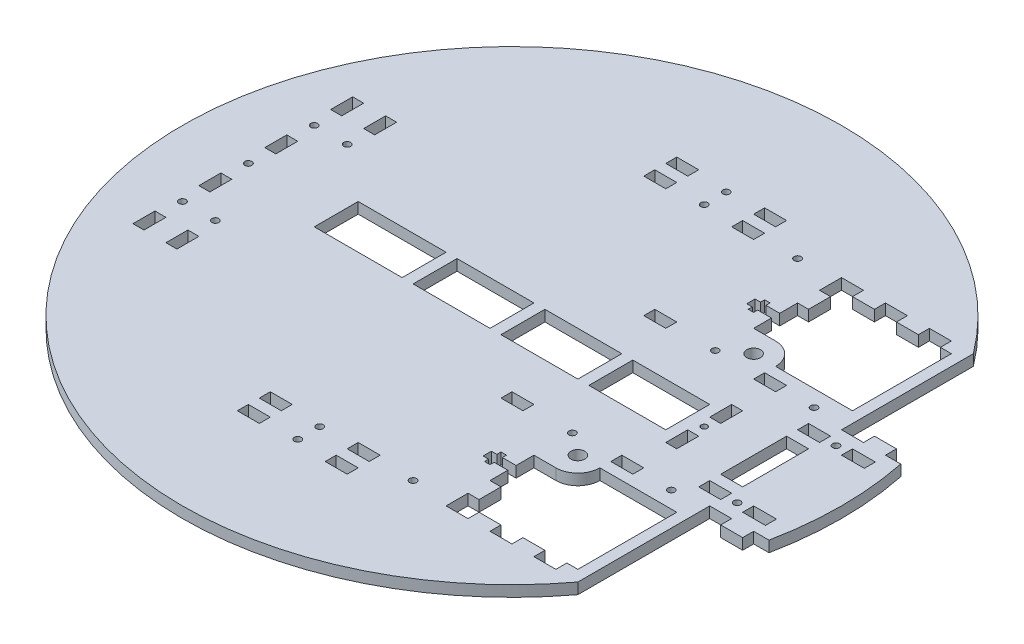
SolidWorks part; units mm, degrees
note: The reader was unsure of these and kept them because the rebuilt part matched: shared geometry of "Sketch6<3>".
ref_plane "Front Plane" through (0, 0, 0) normal (0, 0, 1) x (1, 0, 0)
ref_plane "Top Plane" through (0, 0, 0) normal (0, 1, 0) x (1, 0, 0)
ref_plane "Right Plane" through (0, 0, 0) normal (1, 0, 0) x (0, 0, -1)
sketch "Sketch2" plane through (0, 0, 0) normal (0, 1, 0) x (1, 0, 0)
  circle A0 centre (0, 0) radius 190.5
  dimension "D1" = 381
extrude "Boss-Extrude1" add sketch "Sketch2" along normal blind 6.35
sketch "Sketch5" plane through (0, 6.35, 0) normal (0, 1, 0) x (1, 0, 0)
  line L0 (19.05, 114.3) -> (19.05, 107.95)
  line L2 (19.05, 120.65) -> (31.75, 120.65)
  line L3 (-31.75, 114.3) -> (-19.05, 114.3)
  line L4 (-31.75, 114.3) -> (-31.75, 107.95)
  line L5 (-31.75, 107.95) -> (-19.05, 107.95)
  line L6 (19.05, 120.65) -> (19.05, 127)
  line L7 (19.05, 127) -> (31.75, 127)
  line L8 (31.75, 120.65) -> (31.75, 127)
  line L9 (-31.75, 120.65) -> (-31.75, 127)
  line L10 (-19.05, 127) -> (-31.75, 127)
  line L11 (-19.05, 120.65) -> (-19.05, 127)
  line L12 (-19.05, 120.65) -> (-31.75, 120.65)
  line L13 (-19.05, 114.3) -> (-19.05, 107.95)
  line L14 (31.75, 107.95) -> (19.05, 107.95)
  line L15 (31.75, 114.3) -> (31.75, 107.95)
  line L16 (31.75, 114.3) -> (19.05, 114.3)
  line L18 (31.75, -114.3) -> (19.05, -114.3)
  line L19 (31.75, -114.3) -> (31.75, -107.95)
  line L20 (31.75, -107.95) -> (19.05, -107.95)
  line L21 (-19.05, -114.3) -> (-19.05, -107.95)
  line L22 (-19.05, -120.65) -> (-31.75, -120.65)
  line L23 (-19.05, -120.65) -> (-19.05, -127)
  line L24 (-19.05, -127) -> (-31.75, -127)
  line L25 (-31.75, -120.65) -> (-31.75, -127)
  line L26 (31.75, -120.65) -> (31.75, -127)
  line L27 (19.05, -127) -> (31.75, -127)
  line L28 (19.05, -120.65) -> (19.05, -127)
  line L29 (-31.75, -107.95) -> (-19.05, -107.95)
  line L30 (-31.75, -114.3) -> (-31.75, -107.95)
  line L31 (-31.75, -114.3) -> (-19.05, -114.3)
  line L32 (19.05, -120.65) -> (31.75, -120.65)
  line L33 (19.05, -114.3) -> (19.05, -107.95)
  circle A0 centre (0, 123.825) radius 2
  circle A1 centre (0, 111.125) radius 2
  circle A2 centre (0, -111.125) radius 2
  circle A3 centre (0, -123.825) radius 2
  circle A4 centre (53.975, 111.125) radius 2
  circle A5 centre (53.975, -111.125) radius 2.032
  dimension "D3" = 4
  dimension "D8" = 4
  dimension "D11" = 4
  dimension "D12" = 4.064
  dimension "D1" = 114.3
  dimension "D2" = 0
  dimension "D4" = 6.35
  dimension "D5" = 6.35
  dimension "D6" = 38.1
  dimension "D7" = 12.7
  dimension "D9" = 127
  dimension "D10" = 22.225
  dimension "D13" = 22.225
extrude "Cut-Extrude1" cut sketch "Sketch5" against normal blind 6.35
sketch "Sketch6" plane through (0, 6.35, 0) normal (0, 1, 0) x (1, 0, 0)
  line L0 (0, 0) -> (-152.4, 0)
  line L2 (-155.575, 25.4) -> (-155.575, 12.7)
  line L3 (-155.575, 25.4) -> (-149.225, 25.4)
  line L5 (-155.575, 12.7) -> (-149.225, 12.7)
  line L6 (-149.225, 25.4) -> (-149.225, 12.7)
  line L7 (-149.225, -25.4) -> (-149.225, -12.7)
  line L8 (-155.575, -12.7) -> (-149.225, -12.7)
  line L10 (-155.575, -25.4) -> (-149.225, -25.4)
  line L11 (-155.575, -25.4) -> (-155.575, -12.7)
  line L12 (-149.225, -63.5) -> (-149.225, -50.8)
  line L13 (-155.575, 63.5) -> (-149.225, 63.5)
  line L14 (-155.575, 63.5) -> (-155.575, 50.8)
  line L15 (-155.575, 50.8) -> (-149.225, 50.8)
  line L16 (-149.225, 63.5) -> (-149.225, 50.8)
  line L17 (-155.575, -50.8) -> (-149.225, -50.8)
  line L18 (-155.575, -63.5) -> (-155.575, -50.8)
  line L19 (-155.575, -63.5) -> (-149.225, -63.5)
  circle A0 centre (-152.4, 0) radius 2.032
  circle A1 centre (-152.4, 38.1) radius 2
  circle A2 centre (-152.4, -38.1) radius 2
  dimension "D4" = 4.064
  dimension "D9" = 4
  dimension "D2" = 12.7
  dimension "D3" = 12.7
  dimension "D5" = 152.4
  dimension "D6" = 25.4
  dimension "D7" = 12.7
  dimension "D8" = 6.35
  dimension "D10" = 12.7
extrude "Cut-Extrude2" cut sketch "Sketch6" against normal blind 6.35 contours L2 L5 L6 L3 | A0 | L8 L7 L10 L11
sketch "Sketch7" plane through (0, 6.35, 0) normal (0, 1, 0) x (1, 0, 0)
  line L0 (0, 0) -> (169.1329, 0)
  line L1 (101.6, -50.8) -> (146.05, -50.8)
  line L2 (152.4, 38.1) -> (165.1, 38.1)
  line L3 (76.2, 114.3) -> (88.9, 114.3)
  line L4 (76.2, 114.3) -> (76.2, 101.6)
  line L6 (152.4, 114.3) -> (152.4, 38.1)
  line L8 (88.9, 107.95) -> (101.6, 107.95)
  line L9 (114.3, 107.95) -> (127, 107.95)
  line L10 (146.05, 107.95) -> (146.05, 50.8)
  line L11 (82.55, 101.6) -> (82.55, 88.9)
  line L12 (177.8, 38.1) -> (186.6511, 38.1)
  line L13 (152.4, 38.1) -> (152.4, 114.3)
  line L16 (101.6, 114.3) -> (114.3, 114.3)
  line L19 (114.3, 38.1) -> (114.3, 44.45)
  line L21 (101.6, 38.1) -> (101.6, 44.45)
  line L22 (88.9, 63.5) -> (76.2, 63.5)
  line L23 (127, 114.3) -> (139.7, 114.3)
  line L24 (165.1, 44.45) -> (177.8, 44.45)
  line L25 (76.2, 101.6) -> (76.2, 114.3)
  line L26 (146.05, 107.95) -> (139.7, 107.95)
  line L27 (139.7, 114.3) -> (139.7, 107.95)
  line L28 (139.7, -107.95) -> (146.05, -107.95)
  line L29 (127, 114.3) -> (127, 107.95)
  line L30 (127, 107.95) -> (114.3, 107.95)
  line L31 (114.3, 114.3) -> (114.3, 107.95)
  line L32 (177.8, -38.1) -> (177.8, -44.45)
  line L33 (101.6, 114.3) -> (101.6, 107.95)
  line L34 (101.6, 107.95) -> (88.9, 107.95)
  line L35 (88.9, 114.3) -> (88.9, 107.95)
  line L36 (76.2, 101.6) -> (82.55, 101.6)
  line L37 (76.2, 63.5) -> (76.2, 88.9)
  line L38 (76.2, 88.9) -> (82.55, 88.9)
  line L39 (82.55, 101.6) -> (82.55, 88.9)
  line L40 (76.2, 88.9) -> (76.2, 63.5)
  line L41 (165.1, 38.1) -> (165.1, 44.45)
  line L42 (165.1, 44.45) -> (177.8, 44.45)
  line L43 (177.8, 38.1) -> (177.8, 44.45)
  line L44 (139.7, 107.95) -> (146.05, 107.95)
  line L45 (165.1, -44.45) -> (177.8, -44.45)
  line L46 (165.1, -38.1) -> (165.1, -44.45)
  line L47 (101.6, 38.1) -> (114.3, 38.1)
  line L48 (76.2, -88.9) -> (76.2, -63.5)
  line L49 (82.55, -101.6) -> (82.55, -88.9)
  line L50 (76.2, -88.9) -> (82.55, -88.9)
  line L51 (76.2, -63.5) -> (76.2, -88.9)
  line L52 (76.2, -101.6) -> (82.55, -101.6)
  line L53 (88.9, -114.3) -> (88.9, -107.95)
  line L54 (101.6, -107.95) -> (88.9, -107.95)
  line L55 (101.6, -114.3) -> (101.6, -107.95)
  line L56 (114.3, -114.3) -> (114.3, -107.95)
  line L57 (127, -107.95) -> (114.3, -107.95)
  line L58 (127, -114.3) -> (127, -107.95)
  line L59 (139.7, -114.3) -> (139.7, -107.95)
  line L60 (146.05, -107.95) -> (139.7, -107.95)
  line L61 (76.2, -101.6) -> (76.2, -114.3)
  line L62 (165.1, -44.45) -> (177.8, -44.45)
  line L63 (127, -114.3) -> (139.7, -114.3)
  line L64 (88.9, -63.5) -> (76.2, -63.5)
  line L70 (101.6, -114.3) -> (114.3, -114.3)
  line L73 (152.4, -38.1) -> (152.4, -114.3)
  line L74 (177.8, -38.1) -> (186.6511, -38.1)
  line L75 (82.55, -101.6) -> (82.55, -88.9)
  line L76 (146.05, -107.95) -> (146.05, -50.8)
  line L77 (114.3, -107.95) -> (127, -107.95)
  line L78 (88.9, -107.95) -> (101.6, -107.95)
  line L79 (152.4, -114.3) -> (152.4, -38.1)
  line L81 (76.2, -114.3) -> (76.2, -101.6)
  line L82 (76.2, -114.3) -> (88.9, -114.3)
  line L83 (152.4, -38.1) -> (165.1, -38.1)
  line L85 (152.4, -114.3) -> (152.4, -38.1)
  line L86 (114.3, 44.45) -> (101.6, 44.45)
  line L88 (101.6, 50.8) -> (146.05, 50.8)
  circle A0 centre (88.9, 50.8) radius 4.0005
  arc A1 (101.6, 50.8) -> (88.9, 63.5) centre (88.9, 50.8) ccw
  circle A2 centre (0, 0) radius 190.5 construction
  arc A3 (101.6, -50.8) -> (88.9, -63.5) centre (88.9, -50.8) cw
  circle A4 centre (88.9, -50.8) radius 4.0005
  arc A5 (186.6511, -38.1) -> (186.6511, 38.1) centre (0, 0) ccw
  arc A6 (152.4, -114.3) -> (152.4, 114.3) centre (0, 0) ccw
  arc A7 (152.4, -114.3) -> (186.6511, -38.1) centre (0, 0) cw
  circle A8 centre (135.8944, 41.275) radius 2.1861
  point P46 (101.6, 63.5)
  point P79 (101.6, -63.5)
  dimension "D21" = 8.001
  dimension "D22" = 12.7
  dimension "D10" = 4.3721
  dimension "D3" = 38.1
  dimension "D4" = 25.4
  dimension "D5" = 6.35
  dimension "D6" = 76.2
  dimension "D7" = 12.7
  dimension "D8" = 6.35
  dimension "D9" = 50.8
  dimension "D12" = 12.7
  dimension "D13" = 25.4
  dimension "D14" = 12.7
  dimension "D15" = 12.7
  dimension "D16" = 12.7
  dimension "D17" = 12.7
  dimension "D18" = 6.35
  dimension "D19" = 12.7
  dimension "D23" = 12.7
  dimension "D24" = 12.7
  dimension "D25" = 25.4
  dimension "D26" = 6.35
extrude "Cut-Extrude3" cut sketch "Sketch7" against normal blind 6.35
sketch "Sketch11" plane through (0, 6.35, 0) normal (0, 1, 0) x (1, 0, 0)
  line L0 (21.7437, 0) -> (28.1615, 0)
  line L1 (101.6, 44.45) -> (114.3, 44.45)
  line L2 (101.6, 44.45) -> (101.6, 38.1)
  line L3 (101.6, 38.1) -> (114.3, 38.1)
  line L4 (114.3, 44.45) -> (114.3, 38.1)
  line L5 (38.1, 44.45) -> (50.8, 44.45)
  line L6 (38.1, 44.45) -> (38.1, 38.1)
  line L7 (38.1, 38.1) -> (50.8, 38.1)
  line L8 (50.8, 44.45) -> (50.8, 38.1)
  line L9 (50.8, -44.45) -> (50.8, -38.1)
  line L10 (38.1, -38.1) -> (50.8, -38.1)
  line L11 (38.1, -44.45) -> (38.1, -38.1)
  line L12 (38.1, -44.45) -> (50.8, -44.45)
  line L13 (114.3, -44.45) -> (114.3, -38.1)
  line L14 (101.6, -38.1) -> (114.3, -38.1)
  line L15 (101.6, -44.45) -> (101.6, -38.1)
  line L16 (101.6, -44.45) -> (114.3, -44.45)
  circle A0 centre (76.2, 41.275) radius 2
  circle A1 centre (133.35, 41.275) radius 2
  circle A2 centre (133.35, -41.275) radius 2
  circle A3 centre (76.2, -41.275) radius 2
  dimension "D9" = 4
  dimension "D10" = 4
  dimension "D1" = 38.1
  dimension "D2" = 6.35
  dimension "D3" = 101.6
  dimension "D4" = 12.7
  dimension "D5" = 50.8
  dimension "D6" = 12.7
  dimension "D7" = 6.35
  dimension "D8" = 38.1
  dimension "D11" = 25.4
  dimension "D12" = 19.05
extrude "Cut-Extrude8" cut sketch "Sketch11" against normal blind 6.35 contours L8 L7 L6 L5 | A0 | L3 L4 L1 L2 | A1 | A2 | L14 L13 L16 L15 | A3 | L10 L9 L12 L11
sketch "Sketch12" plane through (0, 6.35, 0) normal (0, 1, 0) x (1, 0, 0)
  line L1 (152.4, 19.05) -> (139.7, 19.05)
  line L2 (152.4, 19.05) -> (152.4, -19.05)
  line L3 (152.4, -19.05) -> (139.7, -19.05)
  line L4 (139.7, 19.05) -> (139.7, -19.05)
  line L5 (139.7, 25.4) -> (152.4, 25.4)
  line L6 (139.7, 25.4) -> (139.7, 31.75)
  line L7 (139.7, 31.75) -> (152.4, 31.75)
  line L8 (152.4, 25.4) -> (152.4, 31.75)
  line L9 (178.2912, -31.75) -> (178.2912, -25.4)
  line L10 (165.1, 31.75) -> (178.2912, 31.75)
  line L11 (165.1, 31.75) -> (165.1, 25.4)
  line L12 (165.1, 25.4) -> (178.2912, 25.4)
  line L13 (178.2912, 31.75) -> (178.2912, 25.4)
  line L14 (165.1, -25.4) -> (178.2912, -25.4)
  line L15 (165.1, -31.75) -> (165.1, -25.4)
  line L16 (165.1, -31.75) -> (178.2912, -31.75)
  line L17 (152.4, -25.4) -> (152.4, -31.75)
  line L18 (139.7, -31.75) -> (152.4, -31.75)
  line L19 (139.7, -25.4) -> (139.7, -31.75)
  line L20 (139.7, -25.4) -> (152.4, -25.4)
  line L21 (107.95, 19.05) -> (114.3, 19.05)
  line L22 (107.95, 19.05) -> (107.95, 6.35)
  line L23 (107.95, 6.35) -> (114.3, 6.35)
  line L24 (114.3, 19.05) -> (114.3, 6.35)
  line L25 (107.95, -6.35) -> (114.3, -6.35)
  line L26 (107.95, -6.35) -> (107.95, -19.05)
  line L27 (107.95, -19.05) -> (114.3, -19.05)
  line L28 (114.3, -6.35) -> (114.3, -19.05)
  circle A0 centre (158.75, 28.575) radius 2
  circle A1 centre (158.75, -28.575) radius 2
  circle A2 centre (111.125, 0) radius 1.7488
  dimension "D7" = 4
  dimension "D17" = 28.575
  dimension "D1" = 19.05
  dimension "D2" = 19.05
  dimension "D3" = 12.7
  dimension "D4" = 139.7
  dimension "D5" = 6.35
  dimension "D6" = 6.35
  dimension "D8" = 3.175
  dimension "D9" = 12.7
  dimension "D10" = 6.35
  dimension "D11" = 0
  dimension "D12" = 6.35
  dimension "D13" = 6.35
  dimension "D14" = 6.35
  dimension "D15" = 25.4
  dimension "D16" = 25.4
  dimension "D18" = 12.7
  dimension "D19" = 12.7
  dimension "D20" = 12.7
  dimension "D21" = 6.35
extrude "Cut-Extrude9" cut sketch "Sketch12" against normal blind 6.35
sketch "Sketch13" plane through (0, 6.35, 0) normal (0, 1, 0) x (1, 0, 0)
  line L2 (65.0875, 73.8188) -> (65.0875, 71.4375)
  line L4 (76.2, 73.8188) -> (76.2, 78.5813)
  line L5 (76.2, 78.5813) -> (68.2625, 78.5813)
  line L13 (65.0875, 78.5813) -> (61.9125, 78.5813)
  line L14 (61.9125, 73.8188) -> (61.9125, 78.5813)
  line L16 (68.2625, 78.5813) -> (68.2625, 80.9625)
  line L17 (68.2625, 80.9625) -> (65.0875, 80.9625)
  line L18 (65.0875, 78.5813) -> (65.0875, 80.9625)
  line L19 (68.2625, 71.4375) -> (65.0875, 71.4375)
  line L20 (68.2625, 73.8188) -> (68.2625, 71.4375)
  line L22 (65.0875, 73.8188) -> (61.9125, 73.8188)
  line L24 (76.2, 73.8188) -> (68.2625, 73.8188)
  line L26 (76.2, -73.8188) -> (68.2625, -73.8188)
  line L28 (65.0875, -73.8188) -> (61.9125, -73.8188)
  line L30 (68.2625, -73.8188) -> (68.2625, -71.4375)
  line L31 (68.2625, -71.4375) -> (65.0875, -71.4375)
  line L32 (65.0875, -78.5813) -> (65.0875, -80.9625)
  line L33 (68.2625, -80.9625) -> (65.0875, -80.9625)
  line L34 (68.2625, -78.5813) -> (68.2625, -80.9625)
  line L36 (61.9125, -73.8188) -> (61.9125, -78.5813)
  line L37 (65.0875, -78.5813) -> (61.9125, -78.5813)
  line L45 (76.2, -78.5813) -> (68.2625, -78.5813)
  line L46 (76.2, -73.8188) -> (76.2, -78.5813)
  line L48 (65.0875, -73.8188) -> (65.0875, -71.4375)
  dimension "D2" = 2.3813
  dimension "D4" = 3.175
extrude "Cut-Extrude10" cut sketch "Sketch13" against normal blind 6.35
sketch "Sketch14" plane through (0, 6.35, 0) normal (0, 1, 0) x (1, 0, 0)
  line L0 (50.8, 12.7) -> (50.8, -12.7)
  line L1 (-101.6, 12.7) -> (-50.8, 12.7)
  line L2 (-101.6, 12.7) -> (-101.6, -12.7)
  line L3 (-101.6, -12.7) -> (-50.8, -12.7)
  line L4 (101.6, 12.7) -> (101.6, -12.7)
  line L5 (-50.8, 12.7) -> (-50.8, -12.7)
  line L6 (-44.45, 12.7) -> (-44.45, -12.7)
  line L7 (6.35, 12.7) -> (6.35, -12.7)
  line L8 (57.15, 12.7) -> (57.15, -12.7)
  line L9 (0, 12.7) -> (0, -12.7)
  line L10 (-44.45, 12.7) -> (0, 12.7)
  line L11 (-44.45, -12.7) -> (0, -12.7)
  line L12 (6.35, -12.7) -> (50.8, -12.7)
  line L13 (6.35, 12.7) -> (50.8, 12.7)
  line L14 (57.15, 12.7) -> (101.6, 12.7)
  line L15 (57.15, -12.7) -> (101.6, -12.7)
  dimension "D1" = 25.4
  dimension "D2" = 12.7
  dimension "D3" = 101.6
  dimension "D4" = 101.6
  dimension "D5" = 6.35
  dimension "D6" = 44.45
  dimension "D7" = 6.35
  dimension "D8" = 44.45
  dimension "D9" = 6.35
extrude "Cut-Extrude12" cut sketch "Sketch14" against normal blind 6.35
extrude "Cut-Extrude13" cut sketch "Sketch6<3>" against normal blind 6.35 contours L16 L15 L14 L13 | A1 | L6 L5 L2 L3 | A0 | L7 L8 L11 L10 | A2 | L12 L17 L18 L19
sketch "Sketch6<3>" plane through (0, 6.35, 0) normal (0, 1, 0) x (1, 0, 0) same geometry as "Sketch6"
sketch "Sketch17" plane through (0, 6.35, 0) normal (0, 1, 0) x (1, 0, 0)
  line L0 (0, 0) -> (-133.35, 0)
  line L1 (-130.175, -50.8) -> (-130.175, -63.5)
  line L2 (-136.525, 50.8) -> (-130.175, 50.8)
  line L3 (-136.525, 50.8) -> (-136.525, 63.5)
  line L4 (-136.525, 63.5) -> (-130.175, 63.5)
  line L5 (-130.175, 50.8) -> (-130.175, 63.5)
  line L6 (-136.525, -63.5) -> (-130.175, -63.5)
  line L7 (-136.525, -50.8) -> (-136.525, -63.5)
  line L8 (-136.525, -50.8) -> (-130.175, -50.8)
  circle A0 centre (-133.35, 38.1) radius 2
  circle A1 centre (-133.35, -38.1) radius 2
  dimension "D5" = 4
  dimension "D1" = 133.35
  dimension "D2" = 6.35
  dimension "D3" = 12.7
  dimension "D4" = 130.175
  dimension "D6" = 38.1
  dimension "D7" = 133.35
extrude "Cut-Extrude14" cut sketch "Sketch17" against normal blind 6.35 contours L5 L4 L3 L2 | A0 | A1 | L8 L1 L6 L7
